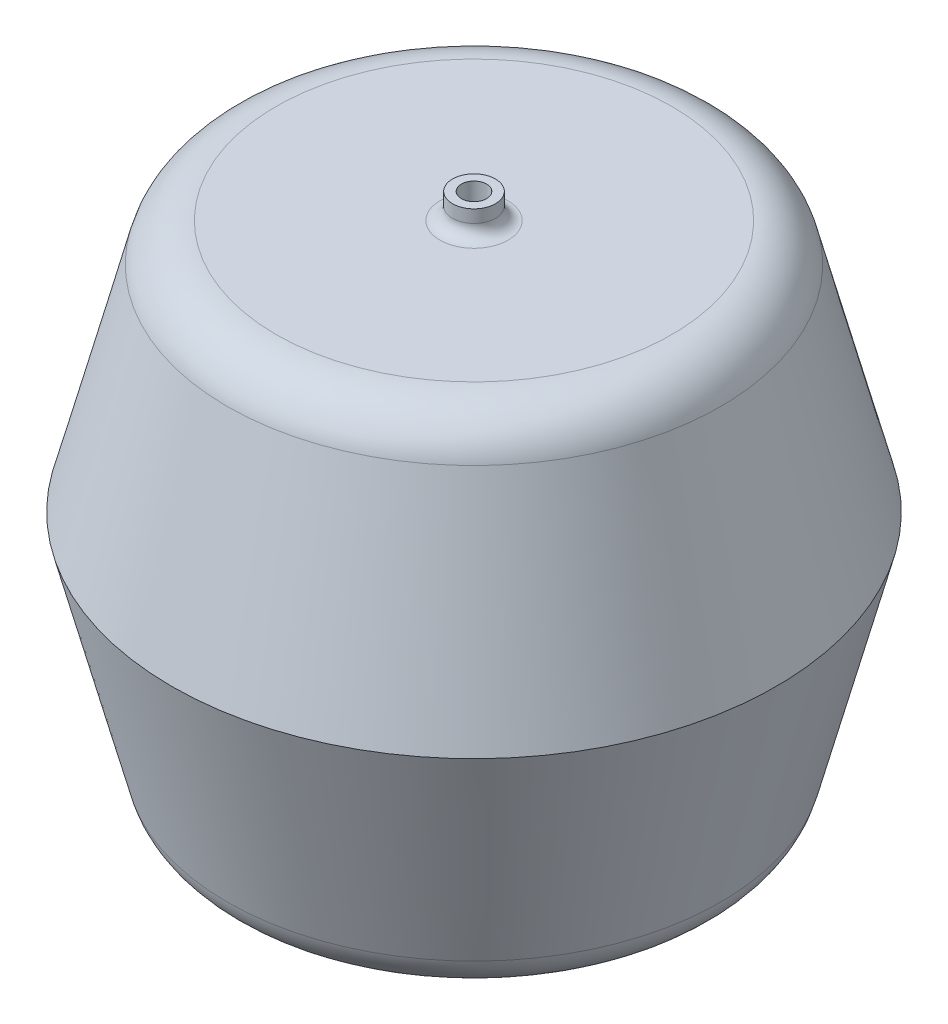
SolidWorks part; units mm, degrees
ref_plane "Front Plane" through (0, 0, 0) normal (0, 0, 1) x (1, 0, 0)
ref_plane "Top Plane" through (0, 0, 0) normal (0, 1, 0) x (1, 0, 0)
ref_plane "Right Plane" through (0, 0, 0) normal (1, 0, 0) x (0, 0, -1)
sketch "Sketch1" plane through (0, 0, 0) normal (0, 0, 1) x (1, 0, 0)
  line L0 (0, 0) -> (238.2977, 0)
  line L1 (238.2977, 0) -> (304.038, 254)
  line L2 (304.038, 254) -> (238.2977, 508)
  line L3 (238.2977, 508) -> (0, 508)
  line L4 (0, 12.7) -> (228.4663, 12.7)
  line L5 (228.4663, 12.7) -> (290.9195, 254)
  line L6 (290.9195, 254) -> (228.4663, 495.3)
  line L7 (228.4663, 495.3) -> (0, 495.3)
  line L8 (0, 508) -> (0, 495.3)
  line L9 (0, 12.7) -> (0, 0)
  dimension "D1" = 238.2977
  dimension "D2" = 254
  dimension "D3" = 304.038
  dimension "D4" = 254
  dimension "D5" = 12.7
revolve "Revolve1" add sketch "Sketch1" angle 360 about L8
fillet "Fillet1" radius 50.8 2 edges at (0, 0, 238.2977) (0, 508, 238.2977)
sketch "Sketch2" plane through (0, 0, 0) normal (0, -1, 0) x (1, 0, 0)
  circle A0 centre (0, 0) radius 152.019
  dimension "D1" = 304.038
extrude "Boss-Extrude1" add sketch "Sketch2" along normal blind 25.4
sketch "Sketch3" plane through (0, 508, 0) normal (0, 1, 0) x (1, 0, 0)
  circle A0 centre (0, 0) radius 21.59
  dimension "D1" = 43.18
extrude "Boss-Extrude2" add sketch "Sketch3" along normal blind 25.4
fillet "Fillet2" radius 12.7 1 edges at (0, 508, -21.59)
sketch "Sketch4" plane through (0, 533.4, 0) normal (0, 1, 0) x (1, 0, 0)
  circle A0 centre (0, 0) radius 12.7
  dimension "D1" = 25.4
extrude "Cut-Extrude1" cut sketch "Sketch4" against normal blind 38.1
